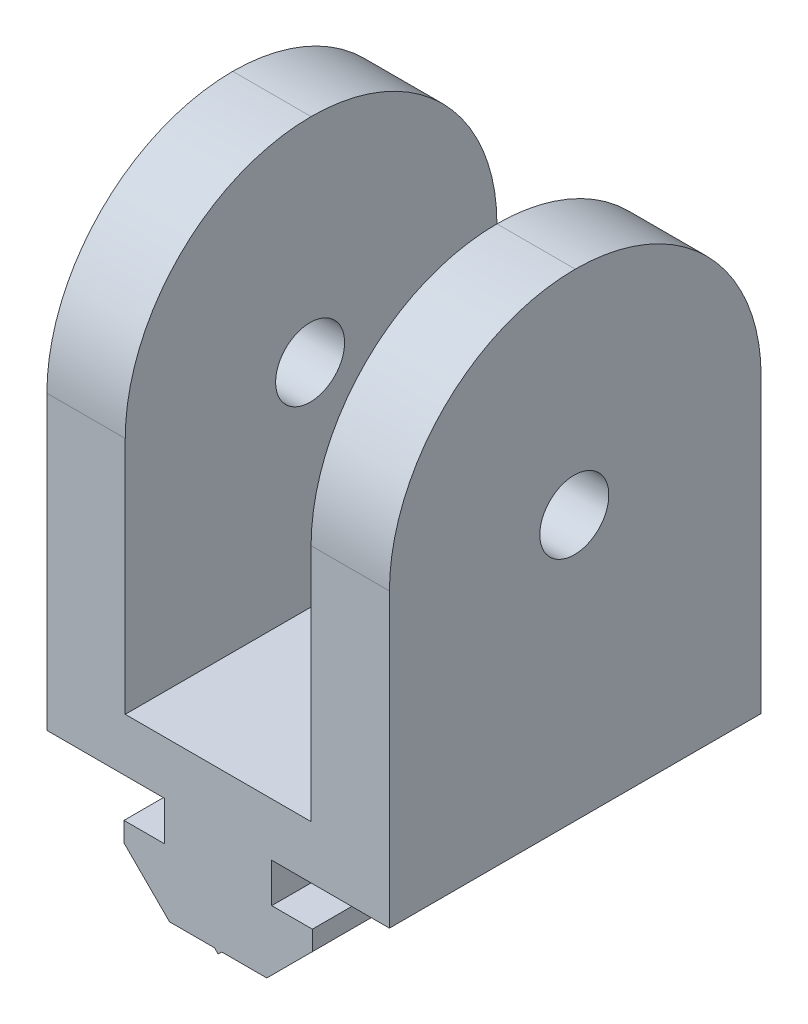
SolidWorks part; units mm, degrees
material "Beech"
ref_plane "Front Plane" through (0, 0, 0) normal (0, 0, 1) x (1, 0, 0)
ref_plane "Top Plane" through (0, 0, 0) normal (0, 1, 0) x (1, 0, 0)
ref_plane "Right Plane" through (0, 0, 0) normal (1, 0, 0) x (0, 0, -1)
sketch "Sketch1" plane through (0, 0, 0) normal (0, 1, 0) x (1, 0, 0)
  line L1 (-60.7745, 29.9716) -> (89.2255, 29.9716)
  line L2 (-60.7745, 29.9716) -> (-60.7745, -40.0284)
  line L3 (-60.7745, -40.0284) -> (89.2255, -40.0284)
  line L4 (89.2255, 29.9716) -> (89.2255, -40.0284)
  dimension "D1" = 150
  dimension "D2" = 70
extrude "Boss-Extrude1" add sketch "Sketch1" along normal blind 10
sketch "Sketch2" plane through (0, 10, 0) normal (0, 1, 0) x (1, 0, 0)
  line L0 (89.2255, 29.9716) -> (-60.7745, 29.9716) construction
  line L1 (-40.7745, 29.9716) -> (-22.7745, 29.9716)
  line L2 (-40.7745, 29.9716) -> (-40.7745, -40.0284)
  line L3 (-40.7745, -40.0284) -> (-22.7745, -40.0284)
  line L4 (-22.7745, 29.9716) -> (-22.7745, -40.0284)
  line L5 (-60.7745, -40.0284) -> (89.2255, -40.0284) construction
  line L6 (-60.7745, 29.9716) -> (-60.7745, -40.0284) construction
  line L7 (12.2255, 29.9716) -> (30.2255, 29.9716)
  line L8 (12.2255, 29.9716) -> (12.2255, -40.0284)
  line L9 (12.2255, -40.0284) -> (30.2255, -40.0284)
  line L10 (30.2255, 29.9716) -> (30.2255, -40.0284)
  dimension "D1" = 18
  dimension "D2" = 35
  dimension "D3" = 18
  dimension "D4" = 20
extrude "Boss-Extrude2" add sketch "Sketch2" along normal blind 80
fillet "Fillet1" radius 35 4 edges at (21.2255, 90, 40.0284) (21.2255, 90, -29.9716) (-31.7745, 90, -29.9716) (-31.7745, 90, 40.0284)
sketch "Sketch3" plane through (-40.7745, 0, 0) normal (-1, 0, 0) x (0, 0, 1)
  line L0 (-29.9716, 10) -> (40.0284, 10) construction
  circle A0 centre (5.212, 50) radius 6.5
  dimension "D1" = 13
  dimension "D2" = 40
extrude "Cut-Extrude1" cut sketch "Sketch3" against normal through all
sketch "Sketch5" plane through (0, 0, 0) normal (0, 0, 1) x (1, 0, 0)
  line L0 (30.2255, 40.3886) -> (74.056, 10)
  line L1 (30.2255, 55) -> (30.2255, 10) construction
  line L2 (30.2255, 10) -> (89.2255, 10) construction
rib "Rib1" sketch "Sketch5" sketch "Sketch5" thickness 40 extrusion direction parallel to sketch draft on no parameters "D1"=40
sketch "Sketch7" plane through (0, 10, 0) normal (0, 1, 0) x (1, 0, 0)
  line L0 (30.2255, -5.0284) -> (30.2255, 9.9716)
  line L1 (30.2255, -5.0284) -> (30.2255, 29.9716) construction
  line L2 (30.2255, 20) -> (30.2255, 29.9716) construction
  line L3 (30.2255, 20) -> (74.056, 20)
  line L4 (30.2255, 20) -> (30.2255, 9.9716)
  line L5 (30.2255, 9.9716) -> (74.056, 9.9716)
  line L6 (74.056, 20) -> (74.056, 9.9716)
  line L7 (74.056, -20) -> (74.056, 20) construction
  line M8 (30.2255, 20) -> (74.056, 20)
  line M9 (74.056, 20) -> (74.056, -20)
  dimension "D1" = 15
extrude "Cut-Extrude2" cut sketch "Sketch7" along normal blind 80 contours L4 L5 M9 M8 region at (52.1407, 10, -14.9858)
scale "Scale1" scale about origin uniform scaling yes scale factor 0.31
sketch "Sketch10" plane through (0, 0, -9.2912) normal (0, 0, -1) x (-1, 0, 0)
  line L0 (1.6351, 3.1) -> (1.6351, 28.4889) construction
  line L1 (-3.7899, 3.1) -> (7.0601, 3.1) construction
  line L2 (1.6351, 3.1) -> (1.6351, 0) construction
  line L3 (-27.6599, 0) -> (18.8401, 0) construction
  line L4 (4.7601, 0) -> (4.7601, -2.3)
  line L5 (-1.4899, 0) -> (-3.8649, 0)
  line L6 (-1.4899, 0) -> (-1.4899, -2.3)
  line L7 (-1.4899, -2.3) -> (-3.8649, -2.3)
  line L8 (-3.8649, 0) -> (-3.8649, -2.3)
  line L9 (4.7601, -2.3) -> (7.1351, -2.3)
  line B0 (1.6351, -10) -> (1.6351, 0) construction
  line B1 (1.6351, -6.31) -> (1.4251, -6.1)
  line B2 (1.4251, -6.1) -> (-1.2042, -6.1)
  line B3 (-1.2042, -6.1) -> (-3.8649, -3.4393)
  line B4 (-3.8649, -3.4393) -> (-3.8649, -1.8)
  line B5 (-3.8649, -1.8) -> (-1.4899, -1.8)
  line B6 (-1.4899, -1.8) -> (-1.4899, -1.455)
  line B7 (-1.4899, -1.455) -> (-2.9449, 0)
  line B8 (-2.9449, 0) -> (6.2151, 0)
  line B9 (1.6351, -10) -> (-4.2781, -4.0868) construction
  line B10 (4.7601, -1.455) -> (6.2151, 0)
  line B11 (4.7601, -1.8) -> (4.7601, -1.455)
  line B12 (7.1351, -1.8) -> (4.7601, -1.8)
  line B13 (7.1351, -3.4393) -> (7.1351, -1.8)
  line B14 (4.4744, -6.1) -> (7.1351, -3.4393)
  line B15 (1.8451, -6.1) -> (4.4744, -6.1)
  line B16 (1.6351, -6.31) -> (1.8451, -6.1)
  line M12 (-27.6599, 0) -> (18.8401, 0)
  dimension "D1" = 0.5
sketch_block_instance "V Slot 1-1"
sketch_block "V Slot 1" parameters "D1"=10, "D2"=11, "D3"=4.3, "D4"=1.8, "D5"=0.21, "D6"=45, "D7"=9.16, "D8"=1.5, "D9"=6.25
extrude "Boss-Extrude4" add sketch "Sketch10" against normal up to surface (21.7 mm away) contours B1 B16 B15 B14 B13 L9 L4 L6 L7 B4 B3 B2 M12 region at (-1.6351, -3.1636, -9.2912)
sketch "Sketch11" plane through (0, 0, -9.2912) normal (0, 0, -1) x (-1, 0, 0)
  line L0 (1.6351, 3.1) -> (1.6351, 27.8689) construction
  line L1 (-3.7899, 3.1) -> (7.0601, 3.1) construction
  line L2 (-8.3649, 3.1) -> (-8.3649, 27.9)
  line L3 (-9.3699, 3.1) -> (12.6401, 3.1)
  line L4 (-9.3699, 3.1) -> (-9.3699, 27.9)
  line L5 (-9.3699, 27.9) -> (12.6401, 27.9)
  line L6 (12.6401, 3.1) -> (12.6401, 27.9)
  line L7 (11.6351, 3.1) -> (11.6351, 27.9)
  line L8 (-8.3649, 3.1) -> (-8.3649, 0)
  line L9 (-27.6599, 0) -> (-1.4899, 0) construction
  line L10 (11.6351, 3.1) -> (11.6351, 0)
  line L11 (4.7601, 0) -> (18.8401, 0) construction
  line L15 (-22.9574, 3.1) -> (-9.3699, 3.1)
  line L16 (-9.3699, 3.1) -> (-9.3699, 12.5205)
  line L17 (-9.3699, 12.5205) -> (-22.9574, 3.1)
  line L18 (-22.9574, 3.1) -> (-9.3699, 3.1)
  line L19 (-9.3699, 3.1) -> (-9.3699, 12.5205)
  line L20 (-9.3699, 12.5205) -> (-22.9574, 3.1)
  line M4 (-3.7899, 17.05) -> (-9.3699, 17.05)
  line M5 (-9.3699, 17.05) -> (-9.3699, 3.1)
  line M6 (-9.3699, 3.1) -> (-27.6599, 3.1)
  line M7 (-27.6599, 3.1) -> (-27.6599, 0)
  line M8 (-27.6599, 0) -> (-1.4899, 0)
  line M21 (4.7601, 0) -> (18.8401, 0)
  line M22 (18.8401, 0) -> (18.8401, 3.1)
  line M23 (18.8401, 3.1) -> (12.6401, 3.1)
  line M24 (12.6401, 3.1) -> (12.6401, 17.05)
  line M25 (12.6401, 17.05) -> (7.0601, 17.05)
  dimension "D1" = 10
  dimension "D2" = 0
extrude "Cut-Extrude5" cut sketch "Sketch11" against normal up to surface (21.7 mm away) contours L4 L3 L2 M5 M4 | L5 L4 L2 M4 | L4 L20 M6 | L8 L3 M6 M7 M8 | L7 L3 M24 M25 | L7 L6 L5 M25 | L3 L10 M21 M22 M23 region at (8.8674, 10.075, -9.2912) region at (18.0124, 1.55, -9.2912) region at (8.8674, 22.475, -9.2912) region at (13.899, 6.2402, -9.2912) region at (-12.1376, 10.075, -9.2912) region at (-15.2376, 1.55, -9.2912) region at (-12.1376, 22.475, -9.2912)
